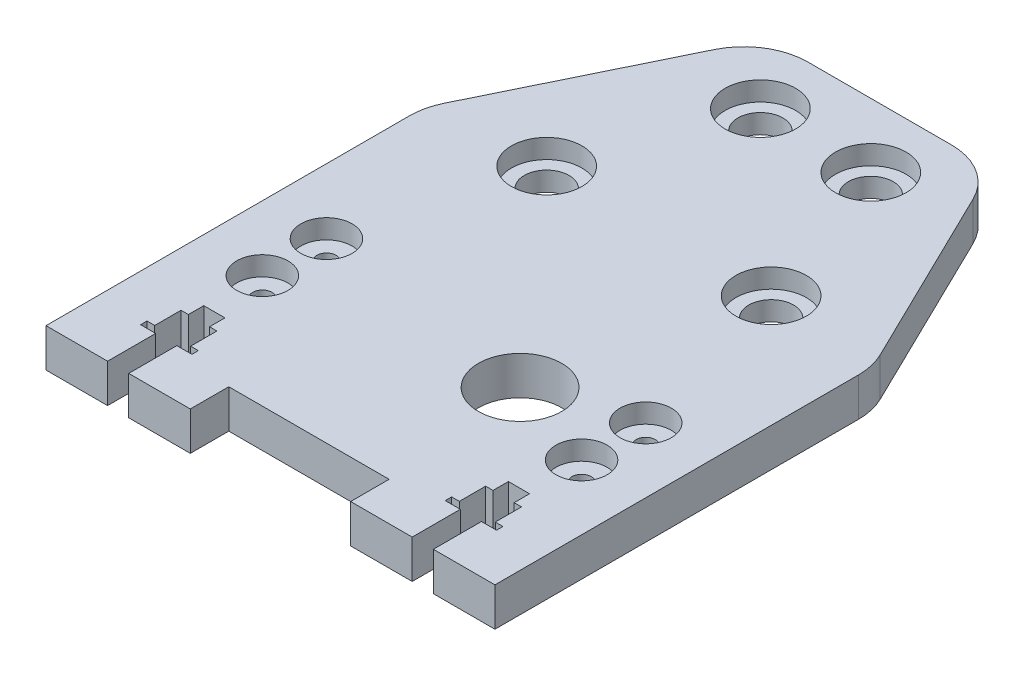
SolidWorks part; units mm, degrees
material "Acrylic (Medium-high impact)"
ref_plane "Front Plane" through (0, 0, 0) normal (0, 0, 1) x (1, 0, 0)
ref_plane "Top Plane" through (0, 0, 0) normal (0, 1, 0) x (1, 0, 0)
ref_plane "Right Plane" through (0, 0, 0) normal (1, 0, 0) x (0, 0, -1)
sketch "Sketch1" plane through (0, 0, 0) normal (0, 1, 0) x (1, 0, 0)
  line L0 (0, 16.0328) -> (0, -11.4098) construction
  line L1 (-38.0739, 0) -> (41.7971, 0) construction
  line L2 (8.6075, -9.22) -> (17.5, -33.652) construction
  line L3 (-8.6075, -9.22) -> (-17.5, -33.652) construction
  line L4 (17.5, -33.652) -> (10.3, -65.6008) construction
  line L5 (24.8896, -70.6008) -> (-24.8896, -70.6008) construction
  line L6 (-17.4416, 0.78) -> (-35, -35.22)
  line L7 (-35, -94.22) -> (35, -94.22)
  line L8 (-35, -94.22) -> (-35, 0.78)
  line L9 (-35, 0.78) -> (35, 0.78)
  line L10 (35, -94.22) -> (35, 0.78)
  line L11 (-35, -94.22) -> (35, 0.78) construction
  line L12 (-35, 0.78) -> (35, -94.22) construction
  line L13 (17.4416, 0.78) -> (35, -35.22)
  line L15 (-12.5, -88.22) -> (12.5, -88.22)
  line L16 (-12.5, -88.22) -> (-12.5, -94.22)
  line L17 (-12.5, -94.22) -> (12.5, -94.22)
  line L18 (12.5, -88.22) -> (12.5, -94.22)
  line L19 (-12.5, -88.22) -> (12.5, -94.22) construction
  line L20 (-12.5, -94.22) -> (12.5, -88.22) construction
  circle A0 centre (17.5, -33.652) radius 23.625 construction
  circle A1 centre (-8.6075, -9.22) radius 3.5
  circle A2 centre (-17.5, -33.652) radius 3.5
  circle A3 centre (17.5, -33.652) radius 3.5
  circle A4 centre (8.6075, -9.22) radius 3.5
  circle A5 centre (10.3, -65.6008) radius 3.5
  circle A6 centre (8.6075, -9.22) radius 5.5
  circle A7 centre (-8.6075, -9.22) radius 5.5
  circle A8 centre (-17.5, -33.652) radius 5.5
  circle A9 centre (17.5, -33.652) radius 5.5
  point P18 (0, -46.72)
  point P28 (0, -91.22)
  arc B0 (3.9, -65.6008) -> (16.7, -65.6008) centre (10.3, -65.6008) ccw construction
  arc B1 (26.7, -59.3508) -> (22.6896, -60.6008) centre (24.8896, -60.6008) ccw construction
  arc B2 (22.6896, -70.6008) -> (26.7, -71.8508) centre (24.8896, -70.6008) ccw construction
  arc B3 (-26.7, -61.8508) -> (-26.7, -59.3508) centre (-24.8896, -60.6008) ccw construction
  arc B4 (-26.7, -71.8508) -> (-26.7, -69.3508) centre (-24.8896, -70.6008) ccw construction
  circle B5 centre (10.3, -65.6008) radius 6.5
  circle B6 centre (24.8896, -60.6008) radius 1.5
  circle B7 centre (24.8896, -70.6008) radius 1.5
  circle B8 centre (-24.8896, -70.6008) radius 1.5
  circle B9 centre (-24.8896, -60.6008) radius 1.5
  dimension "D5" = 47.25
  dimension "D7" = 7
  dimension "D15" = 11
  dimension "D1" = 35
  dimension "D2" = 26
  dimension "D3" = 160
  dimension "D4" = 9.22
  dimension "D6" = 32.75
  dimension "D8" = 95
  dimension "D9" = 70
  dimension "D10" = 10
  dimension "D11" = 26
  dimension "D12" = 59
  dimension "D13" = 25
  dimension "D14" = 6
sketch_block_instance "Block1-1"
sketch_block "Block1" parameters "D1"=3, "D2"=13
ref_axis "Axis1" through (17.5, 0, 33.652) along (0, 1, 0)
ref_axis "Axis2" through (-17.5, -6.1694, 33.652) along (0, 1, 0)
ref_axis "Axis3" through (10.3, 0, 65.6008) along (0, 1, 0)
extrude "Boss-Extrude1" add sketch "Sketch1" along normal blind 6 contours L15 L18 L7 L10 L13 L9 L6 L8 L16 B9 B8 B7 B6 B5 A4 A3 A2 A1 region at (-0.2567, 0, 50.9132)
fillet "Fillet1" radius 10 4 edges at (35, 3, 35.22) (17.4416, 3, -0.78) (-17.4416, 3, -0.78) (-35, 3, 35.22)
sketch "Sketch2" plane through (0, 6, 0) normal (0, 1, 0) x (1, 0, 0)
  circle A0 centre (24.8896, -60.6008) radius 4
  circle A1 centre (24.8896, -70.6008) radius 4
  circle A2 centre (-24.8896, -60.6008) radius 4
  circle A3 centre (-24.8896, -70.6008) radius 4
  dimension "D1" = 8
extrude "Cut-Extrude1" cut sketch "Sketch2" against normal blind 3
extrude "Boss-Extrude2" add sketch "Sketch1<3>" along normal blind 3 contours A8 A2 | A7 A1 | A9 A3 | A6 A4 region at (3.263, 0, 9.22) region at (-13.9519, 0, 9.22) region at (-22.8444, 0, 33.652) region at (12.1556, 0, 33.652)
sketch "Sketch1<3>" plane through (0, 0, 0) normal (0, 1, 0) x (1, 0, 0) same geometry as "Sketch1"
sketch "Sketch3" plane through (0, 6, 0) normal (0, 1, 0) x (1, 0, 0)
  line L0 (23.75, -94.22) -> (23.75, -78.22) construction
  line L1 (12.5, -94.22) -> (35, -94.22) construction
  line L2 (-12.5, -88.22) -> (12.5, -88.22) construction
  line L3 (20.95, -81.62) -> (26.55, -81.62)
  line L4 (20.95, -81.62) -> (20.95, -85.72)
  line L5 (20.95, -85.72) -> (26.55, -85.72)
  line L6 (26.55, -81.62) -> (26.55, -85.72)
  line L7 (20.95, -81.62) -> (26.55, -85.72) construction
  line L8 (20.95, -85.72) -> (26.55, -81.62) construction
  line L9 (19.75, -86.72) -> (27.75, -86.72)
  line L10 (19.75, -86.72) -> (19.75, -85.72)
  line L11 (19.75, -85.72) -> (27.75, -85.72)
  line L12 (27.75, -86.72) -> (27.75, -85.72)
  line L13 (19.75, -86.72) -> (27.75, -85.72) construction
  line L14 (19.75, -85.72) -> (27.75, -86.72) construction
  line L15 (25.4, -79.22) -> (22.1, -79.22)
  line L16 (25.4, -79.22) -> (25.4, -94.22)
  line L17 (25.4, -94.22) -> (22.1, -94.22)
  line L18 (22.1, -79.22) -> (22.1, -94.22)
  line L19 (25.4, -79.22) -> (22.1, -94.22) construction
  line L20 (25.4, -94.22) -> (22.1, -79.22) construction
  point P4 (23.75, -83.67)
  point P9 (23.75, -86.22)
  point P14 (23.75, -86.72)
  point P19 (21.9485, -76.8677)
  line M35 (12.5, -94.22) -> (35, -94.22)
  dimension "D1" = 5.6
  dimension "D2" = 4.1
  dimension "D3" = 8
  dimension "D4" = 1
  dimension "D5" = 15
  dimension "D6" = 3.3
  dimension "D7" = 1.5
extrude "Cut-Extrude2" cut sketch "Sketch3" against normal blind 10 contours L9 L18 L16 M35 | L11 L16 L9 L12 | L11 L18 L9 L16 | L18 L5 L11 L10 L9 | L18 L3 L4 L5 | L3 L18 L11 L16 | L3 L16 L11 L6 | L15 L18 L3 L16 region at (21.525, 6, 83.67) region at (23.75, 6, 80.42) region at (23.75, 6, 83.67) region at (20.925, 6, 86.22) region at (25.975, 6, 83.67) region at (23.75, 6, 86.22) region at (26.575, 6, 86.22) region at (23.75, 6, 90.47)
mirror "Mirror1" about plane through (0, 0, 0) normal (1, 0, 0) of "Cut-Extrude2"
